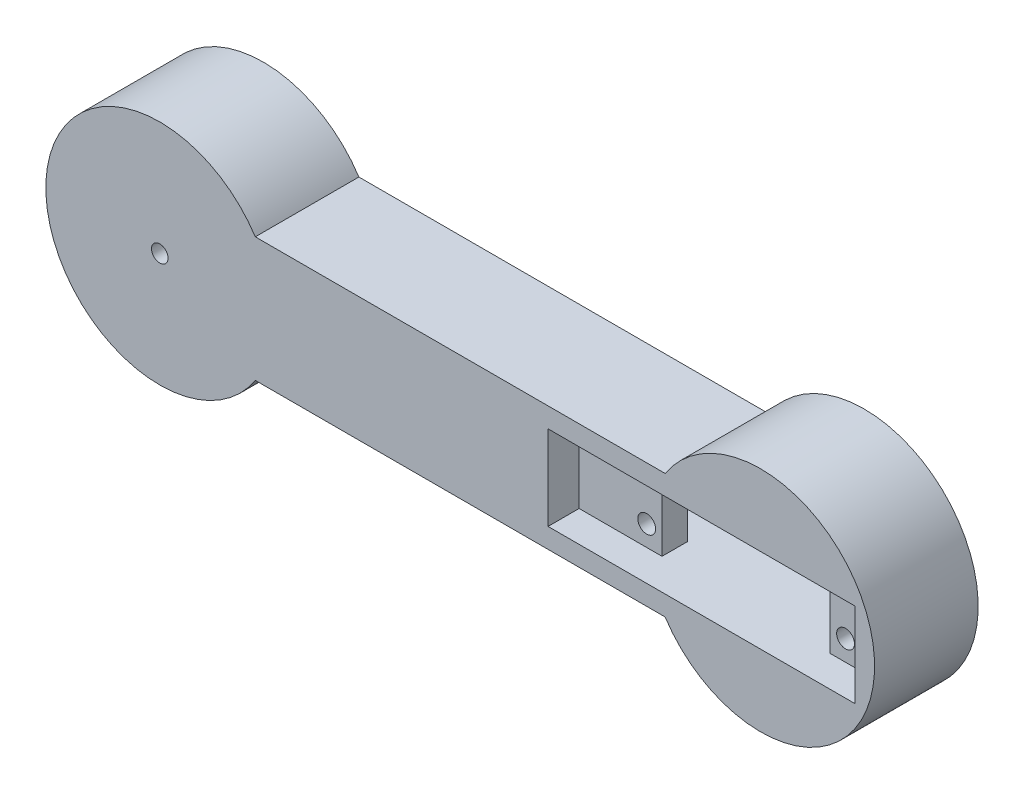
SolidWorks part; units mm, degrees
material "Custom Plastic"
ref_plane "Front Plane" through (0, 0, 0) normal (0, 0, 1) x (1, 0, 0)
ref_plane "Top Plane" through (0, 0, 0) normal (0, 1, 0) x (1, 0, 0)
ref_plane "Right Plane" through (0, 0, 0) normal (1, 0, 0) x (0, 0, -1)
sketch "Sketch1" plane through (0, 0, 0) normal (0, 0, 1) x (1, 0, 0)
  line L1 (0, 15) -> (145, 15)
  line L2 (0, 15) -> (0, -15)
  line L3 (0, -15) -> (145, -15)
  line L4 (145, 15) -> (145, -15)
  circle A0 centre (0, 0) radius 27.5
  circle A1 centre (145, 0) radius 27.5
  circle A2 centre (0, 0) radius 20
  point P9 (0, 0)
  dimension "D1" = 55
  dimension "D4" = 55
  dimension "D5" = 40
  dimension "D2" = 145
  dimension "D3" = 30
extrude "Boss-Extrude1" add sketch "Sketch1" along normal blind 25 contours L3 A1 L1 L4 | A1 L1 A0 L3 | L1 A1 L3 L4 | A2 L3 A0 L1 | A2 L1 A0 L3 | L3 A2 L1 L2 | L1 A2 L3 L2 region at (-6.7804, 0, 0) region at (9.0671, 0, 0) region at (-20.747, 0, 0) region at (21.8665, 0, 0) region at (72.5, 0, 0) region at (151.4116, 0, 0) region at (131.9332, 0, 0)
sketch "Sketch19" plane through (0, 0, 0) normal (0, 0, -1) x (-1, 0, 0)
  circle A0 centre (0, 0) radius 20
extrude "Cut-Extrude14" cut sketch "Sketch19" against normal blind 5 contours A0
sketch "Sketch22" plane through (0, 0, 25) normal (0, 0, 1) x (1, 0, 0)
  circle A0 centre (0, 0) radius 2
  arc A4 (23.0489, 15) -> (23.0489, -15) centre (0, 0) ccw construction
  dimension "D1" = 4
extrude "Cut-Extrude17" cut sketch "Sketch22" against normal up to surface (20 mm away) up to face at (-20, 0, 5)
sketch "Sketch23" plane through (0, 0, 0) normal (0, 0, -1) x (-1, 0, 0)
  line L1 (-106.75, 10.2) -> (-161.25, 10.2)
  line L2 (-106.75, 10.2) -> (-106.75, -10.2)
  line L3 (-106.75, -10.2) -> (-161.25, -10.2)
  line L4 (-161.25, 10.2) -> (-161.25, -10.2)
  line L6 (-107, 0) -> (-106.75, 0)
  line L7 (-107, -3.85) -> (-107, 3.85) construction
  line L8 (-161, 0) -> (-161.25, 0)
  line L10 (-161, -3.85) -> (-161, 3.85) construction
  line L11 (-154, 0) -> (-154.3, 0) construction
  line L12 (-154.3, -10.2) -> (-113.7, -10.2)
  line L13 (-154.3, -10.2) -> (-154.3, 10.2)
  line L14 (-154.3, 10.2) -> (-113.7, 10.2)
  line L15 (-113.7, -10.2) -> (-113.7, 10.2)
  line L16 (-154, -10) -> (-154, 10) construction
  line L17 (-114, 0) -> (-113.7, 0) construction
  line L18 (-114, -10) -> (-114, 10) construction
  dimension "D1" = 54.5
  dimension "D2" = 40.6
  dimension "D3" = 20.4
extrude "Cut-Extrude18" cut sketch "Sketch23" against normal blind 11.3 contours L3 L13 L1 L4 | L3 L15 L1 L13 | L15 L3 L2 L1 | L2 L1 L4 L3 | L13 L12 L15 L14 region at (110.225, 0, 0) region at (134, 0, 0) region at (157.775, 0, 0)
sketch "Sketch24" plane through (0, 0, 11.3) normal (0, 0, -1) x (-1, 0, 0)
  line L0 (-106.75, -10.2) -> (-161.25, -10.2) construction
  line L1 (-154.3, -10.2) -> (-113.7, -10.2)
  line L2 (-154.3, -10.2) -> (-154.3, 10.2)
  line L3 (-154.3, 10.2) -> (-113.7, 10.2)
  line L4 (-113.7, -10.2) -> (-113.7, 10.2)
  line L5 (-106.75, 10.2) -> (-161.25, 10.2) construction
  line L6 (-161.25, -0.6275) -> (-154.3, -0.6275)
  line L7 (-161.25, 10.2) -> (-161.25, -10.2) construction
  line L8 (-113.7, -1) -> (-106.75, -1)
  line L9 (-114, -1) -> (-110.5, -1) construction
  line L10 (-106.75, 10.2) -> (-106.75, -10.2) construction
  line M7 (-161.25, -10.2) -> (-106.75, -10.2)
  line M9 (-106.75, 10.2) -> (-161.25, 10.2)
  dimension "D1" = 40.6
extrude "Cut-Extrude19" cut sketch "Sketch24" against normal up to surface (13.7 mm away) contours L4 L2 M7 M9 region at (134, 0, 11.3) up to face at (2, 0, 25)
sketch "Sketch25" plane through (154.3, 0, 0) normal (-1, 0, 0) x (0, 0, 1)
  line L0 (25, -27.5) -> (25, 27.5) construction
  line L1 (25, 12) -> (17.5, 12)
  line L2 (25, 12) -> (25, -12)
  line L3 (25, -12) -> (17.5, -12)
  line L4 (17.5, 12) -> (17.5, -12)
  line L5 (12.5, 27.5) -> (12.5, 12)
  line L6 (25, 27.5) -> (0, 27.5) construction
  line L7 (12.5, -12) -> (12.5, -27.5)
  line L8 (0, -27.5) -> (25, -27.5) construction
  line M5 (25, -10.2) -> (25, 10.2)
  line M6 (25, 10.2) -> (11.3, 10.2)
  line M8 (11.3, -10.2) -> (25, -10.2)
  dimension "D1" = 24
  dimension "D2" = 7.5
extrude "Cut-Extrude20" cut sketch "Sketch25" against normal blind 13.5 contours L4 M6 M8 M5 region at (154.3, 0, 21.25)
sketch "Sketch26" plane through (113.7, 0, 0) normal (1, 0, 0) x (0, 0, -1)
  line L0 (-16.9501, -10.2) -> (-16.9501, -27.5)
  line L1 (-25, -10.2) -> (-17.5, -10.2)
  line L2 (-25, -10.2) -> (-25, 10.2)
  line L3 (-25, 10.2) -> (-17.5, 10.2)
  line L4 (-17.5, -10.2) -> (-17.5, 10.2)
  line L5 (-25, -27.5) -> (0, -27.5) construction
  line L6 (-21.25, 10.2) -> (-21.25, 27.5)
  line L7 (0, 27.5) -> (-25, 27.5) construction
  line M5 (-25, -10.2) -> (-11.3, -10.2)
  line M7 (-11.3, 10.2) -> (-25, 10.2)
  line M8 (-25, 10.2) -> (-25, -10.2)
  dimension "D1" = 7.5
extrude "Cut-Extrude21" cut sketch "Sketch26" against normal blind 20 contours L4 L3 M5 M7 M8 region at (113.7, 0, 21.25)
sketch "Sketch27" plane through (0, 0, 11.3) normal (0, 0, -1) x (-1, 0, 0)
  line L0 (-161.25, -5.25) -> (-158, -5.25)
  line L1 (-161.25, 10.2) -> (-161.25, -10.2) construction
  line L3 (-158, -5.25) -> (-110, -5.25)
  line L4 (-158, -5.25) -> (-158, 5.25)
  line L5 (-158, 5.25) -> (-110, 5.25)
  line L6 (-110, -5.25) -> (-110, 5.25)
  circle A0 centre (-110, -5.25) radius 2.15
  circle A1 centre (-110, 5.25) radius 2.15
  circle A2 centre (-158, 5.25) radius 2.15
  circle A3 centre (-158, -5.25) radius 2.15
  dimension "D1" = 4.3
extrude "Cut-Extrude22" cut sketch "Sketch27" against normal blind 12 contours L6 A1 L5 | L5 A1 L6 | L6 A0 L3 | L3 A0 L6 | L4 A2 L5 | L5 A2 L4 | A3 region at (158.3042, 5.5542, 11.3) region at (157.0875, 4.3375, 11.3) region at (110.9125, -4.3375, 11.3) region at (109.6958, -5.5542, 11.3) region at (109.6958, 5.5542, 11.3) region at (110.9125, 4.3375, 11.3)
